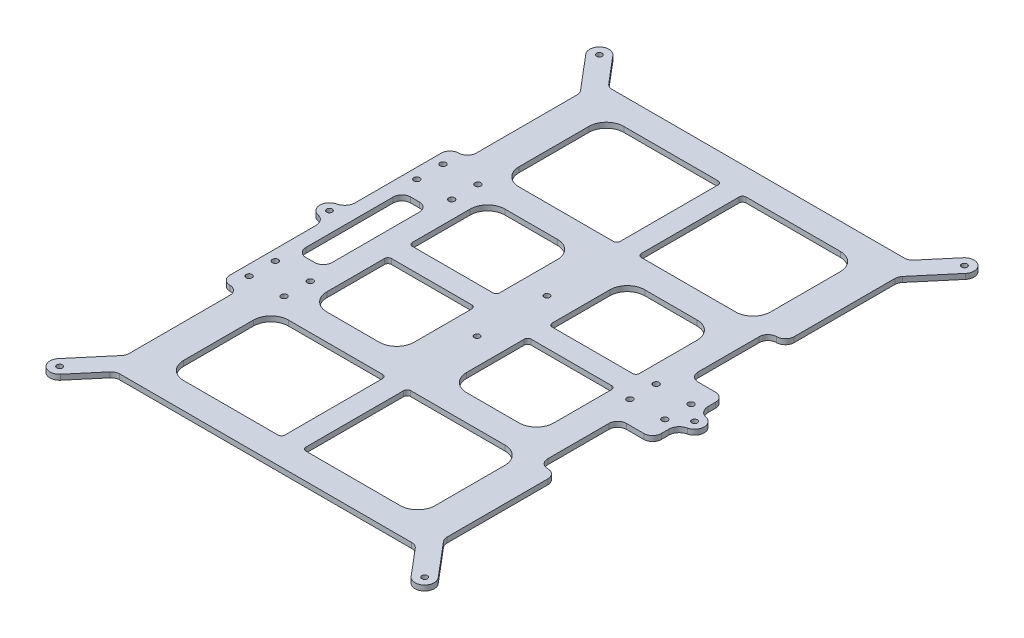
SolidWorks part; units mm, degrees
ref_plane "Alzado" through (0, 0, 0) normal (0, 0, 1) x (1, 0, 0)
ref_plane "Planta" through (0, 0, 0) normal (0, 1, 0) x (1, 0, 0)
ref_plane "Vista lateral" through (0, 0, 0) normal (1, 0, 0) x (0, 0, -1)
sketch "Croquis1" plane through (0, 0, 0) normal (0, 1, 0) x (1, 0, 0)
  line L0 (110, 320) -> (110, 0) construction
  line L1 (0, 0) -> (220, 0)
  line L2 (0, 0) -> (0, 320)
  line L3 (0, 320) -> (220, 320)
  line L4 (220, 0) -> (220, 320)
  line L5 (0, 160) -> (220, 160) construction
  line L6 (19, 320) -> (19, 0) construction
  line L7 (31, 320) -> (31, 0) construction
  line L8 (189, 320) -> (189, 0) construction
  line L9 (201, 320) -> (201, 0) construction
  line L10 (195, 320) -> (195, 0) construction
  line L11 (25, 320) -> (25, 0) construction
  line L12 (5.5, 314.5) -> (5.5, 160) construction
  circle A0 centre (185, 167.5) radius 1.7
  circle A1 centre (205, 167.5) radius 1.7
  circle A4 centre (185, 152.5) radius 1.7
  circle A5 centre (205, 152.5) radius 1.7
  circle A7 centre (35, 215.5) radius 1.7
  circle A8 centre (35, 200.5) radius 1.7
  circle A10 centre (35, 119.5) radius 1.7
  circle A13 centre (35, 104.5) radius 1.7
  circle A14 centre (5.5, 314.5) radius 1.6
  circle A15 centre (214.5, 314.5) radius 1.6
  circle A16 centre (214.5, 5.5) radius 1.6
  circle A17 centre (5.5, 5.5) radius 1.6
  circle A18 centre (15, 200.5) radius 1.7
  circle A19 centre (15, 215.5) radius 1.7
  circle A20 centre (15, 104.5) radius 1.7
  circle A21 centre (15, 119.5) radius 1.7
  circle A22 centre (110, 180) radius 1.6
  circle A23 centre (110, 140) radius 1.6
  circle A32 centre (5.5, 160) radius 1.6
  circle A37 centre (214.5, 160) radius 1.6
  dimension "D8" = 3.4
  dimension "D13" = 6
  dimension "D14" = 3.4
  dimension "D17" = 3.2
  dimension "D23" = 3.2
  dimension "D18" = 20
  dimension "D1" = 320
  dimension "D2" = 220
  dimension "D3" = 12
  dimension "D4" = 12
  dimension "D5" = 158
  dimension "D6" = 19
  dimension "D7" = 6
  dimension "D9" = 20
  dimension "D10" = 10
  dimension "D11" = 7.5
  dimension "D12" = 7.5
  dimension "D15" = 10
  dimension "D16" = 15
  dimension "D20" = 10
  dimension "D21" = 104.5
  dimension "D24" = 5.5
  dimension "D25" = 5.5
extrude "Saliente-Extruir1" add sketch "Croquis1" along normal blind 3
sketch "Croquis2" plane through (0, 3, 0) normal (0, 1, 0) x (1, 0, 0)
  line L0 (220, 160) -> (0, 160) construction
  line L2 (9, 9) -> (211, 9) construction
  line L3 (220, 0) -> (220, 320) construction
  line L4 (9, 148.775) -> (9, 94.5)
  line L5 (110, 320) -> (110, 0) construction
  line L6 (220, 320) -> (0, 320) construction
  line L7 (0, 0) -> (220, 0) construction
  line L8 (9, 9) -> (211, 9)
  line L9 (211, 9) -> (211, 311)
  line L10 (211, 311) -> (9, 311)
  line L11 (9, 311) -> (9, 9)
  line L15 (9, 225.5) -> (9, 171.225)
  line L16 (9, 225.5) -> (19, 225.5)
  line L18 (19, 94.5) -> (9, 94.5)
  line L19 (19, 94.5) -> (19, 30)
  line L20 (24.1066, 19) -> (195.8934, 19)
  line L21 (210.2988, 1.9504) -> (195.8934, 19)
  line L22 (1.2988, 9.0496) -> (19, 30)
  line L23 (9.7012, 1.9504) -> (24.1066, 19)
  line L24 (9, 148.775) -> (9, 9) construction
  line L25 (19, 148.775) -> (19, 19) construction
  line L26 (19, 19) -> (201, 19) construction
  line L27 (211, 9) -> (211, 311) construction
  line L28 (19, 225.5) -> (19, 290)
  line L29 (24.1066, 301) -> (195.8934, 301)
  line L30 (1.2988, 310.9504) -> (19, 290)
  line L31 (9.7012, 318.0496) -> (24.1066, 301)
  line L32 (0, 320) -> (0, 0) construction
  line L33 (218.7012, 9.0496) -> (201, 30)
  line L34 (201, 19) -> (201, 311) construction
  line L35 (201, 94.5) -> (201, 30)
  line L36 (201, 94.5) -> (211, 94.5)
  line L37 (211, 148.775) -> (211, 94.5)
  line L38 (211, 225.5) -> (211, 171.225)
  line L39 (211, 225.5) -> (201, 225.5)
  line L40 (201, 225.5) -> (201, 290)
  line L41 (218.7012, 310.9504) -> (201, 290)
  line L42 (210.2988, 318.0496) -> (195.8934, 301)
  line L43 (182, 276) -> (182, 236)
  line L44 (102, 286) -> (48, 286)
  line L46 (102, 226) -> (48, 226)
  line L47 (38, 276) -> (38, 236)
  line L48 (118, 226) -> (172, 226)
  line L52 (104, 284) -> (104, 228)
  line L53 (116, 284) -> (116, 228)
  line L54 (118, 286) -> (172, 286)
  line L55 (102, 94) -> (48, 94)
  line L56 (38, 44) -> (38, 84)
  line L57 (102, 34) -> (48, 34)
  line L58 (104, 36) -> (104, 92)
  line L59 (116, 36) -> (116, 92)
  line L60 (118, 34) -> (172, 34)
  line L61 (182, 44) -> (182, 84)
  line L62 (118, 94) -> (172, 94)
  line L63 (45, 152) -> (45, 119)
  line L64 (93, 166) -> (47, 166)
  line L65 (95, 168) -> (95, 201)
  line L66 (85, 211) -> (55, 211)
  line L67 (45, 168) -> (45, 201)
  line L68 (85, 109) -> (55, 109)
  line L69 (95, 152) -> (95, 119)
  line L70 (93, 154) -> (47, 154)
  line L71 (135, 109) -> (165, 109)
  line L72 (175, 152) -> (175, 119)
  line L73 (125, 152) -> (125, 119)
  line L74 (127, 154) -> (173, 154)
  line L75 (127, 166) -> (173, 166)
  line L76 (175, 168) -> (175, 201)
  line L77 (135, 211) -> (165, 211)
  line L78 (125, 168) -> (125, 201)
  arc A2 (1.2988, 9.0496) -> (9.7012, 1.9504) centre (5.5, 5.5) ccw
  arc A3 (4.3043, 165.3685) -> (4.3043, 154.6315) centre (5.5, 160) ccw
  arc A4 (9, 148.775) -> (4.3043, 154.6315) centre (3, 148.775) ccw
  arc A5 (9, 171.225) -> (4.3043, 165.3685) centre (3, 171.225) cw
  circle A6 centre (35, 215.5) radius 1.7 construction
  circle A7 centre (35, 104.5) radius 1.7 construction
  arc A8 (48, 226) -> (38, 236) centre (48, 236) cw
  arc A10 (1.2988, 310.9504) -> (9.7012, 318.0496) centre (5.5, 314.5) cw
  arc A11 (218.7012, 9.0496) -> (210.2988, 1.9504) centre (214.5, 5.5) cw
  arc A12 (211, 148.775) -> (215.6957, 154.6315) centre (217, 148.775) cw
  arc A13 (215.6957, 165.3685) -> (215.6957, 154.6315) centre (214.5, 160) cw
  arc A14 (211, 171.225) -> (215.6957, 165.3685) centre (217, 171.225) ccw
  arc A15 (218.7012, 310.9504) -> (210.2988, 318.0496) centre (214.5, 314.5) ccw
  arc A16 (48, 286) -> (38, 276) centre (48, 276) ccw
  arc A17 (172, 226) -> (182, 236) centre (172, 236) ccw
  arc A18 (172, 286) -> (182, 276) centre (172, 276) cw
  arc A19 (48, 94) -> (38, 84) centre (48, 84) ccw
  arc A20 (48, 34) -> (38, 44) centre (48, 44) cw
  arc A21 (172, 34) -> (182, 44) centre (172, 44) ccw
  arc A22 (172, 94) -> (182, 84) centre (172, 84) cw
  arc A23 (102, 226) -> (104, 228) centre (102, 228) ccw
  arc A24 (102, 286) -> (104, 284) centre (102, 284) cw
  arc A25 (116, 284) -> (118, 286) centre (118, 284) cw
  arc A26 (118, 226) -> (116, 228) centre (118, 228) cw
  arc A27 (116, 92) -> (118, 94) centre (118, 92) cw
  arc A28 (116, 36) -> (118, 34) centre (118, 36) ccw
  arc A29 (102, 34) -> (104, 36) centre (102, 36) ccw
  arc A30 (102, 94) -> (104, 92) centre (102, 92) cw
  arc A31 (95, 201) -> (85, 211) centre (85, 201) ccw
  arc A32 (55, 211) -> (45, 201) centre (55, 201) ccw
  arc A33 (55, 109) -> (45, 119) centre (55, 119) cw
  arc A34 (95, 119) -> (85, 109) centre (85, 119) cw
  arc A35 (165, 109) -> (175, 119) centre (165, 119) ccw
  arc A36 (125, 119) -> (135, 109) centre (135, 119) ccw
  arc A37 (165, 211) -> (175, 201) centre (165, 201) cw
  arc A38 (125, 201) -> (135, 211) centre (135, 201) cw
  arc A39 (127, 166) -> (125, 168) centre (127, 168) cw
  arc A40 (173, 166) -> (175, 168) centre (173, 168) ccw
  arc A41 (175, 152) -> (173, 154) centre (173, 152) ccw
  arc A42 (125, 152) -> (127, 154) centre (127, 152) cw
  arc A43 (45, 152) -> (47, 154) centre (47, 152) cw
  arc A44 (95, 152) -> (93, 154) centre (93, 152) ccw
  arc A45 (93, 166) -> (95, 168) centre (93, 168) ccw
  arc A46 (47, 166) -> (45, 168) centre (47, 168) cw
  point P28 (110, 19)
  point P71 (110, 301)
  point P76 (38, 226)
  point P79 (38, 286)
  point P106 (104, 226)
  point P109 (104, 286)
  point P112 (116, 286)
  point P115 (116, 226)
  point P118 (116, 94)
  point P121 (116, 34)
  point P124 (104, 34)
  point P127 (104, 94)
  point P137 (95, 211)
  point P140 (45, 211)
  point P167 (125, 166)
  point P170 (175, 166)
  point P173 (175, 154)
  point P176 (125, 154)
  point P179 (45, 154)
  point P182 (95, 154)
  point P185 (95, 166)
  point P188 (45, 166)
  dimension "D2" = 11
  dimension "D3" = 11
  dimension "D4" = 6
  dimension "D5" = 10
  dimension "D6" = 10
  dimension "D7" = 60
  dimension "D12" = 10
  dimension "D14" = 2
  dimension "D19" = 10
  dimension "D20" = 2
  dimension "D9" = 30
  dimension "D10" = 15
  dimension "D8" = 19
  dimension "D11" = 38
  dimension "D13" = 6
  dimension "D15" = 6
  dimension "D16" = 15
  dimension "D17" = 50
  dimension "D18" = 45
  dimension "D1" = 9
extrude "Cortar-Extruir1" cut sketch "Croquis2" against normal up to surface (3 mm away) flip side to cut up to face at (5.5, 0, -158.4)
fillet "Redondeo1" radius 5 12 edges at (9, 1.5, -225.5) (9, 1.5, -94.5) (24.1066, 1.5, -301) (195.8934, 1.5, -301) (201, 1.5, -290) (201, 1.5, -30) (195.8934, 1.5, -19) (24.1066, 1.5, -19) (19, 1.5, -30) (19, 1.5, -94.5) (19, 1.5, -290) (19, 1.5, -225.5)
sketch "Croquis3" plane through (0, 3, 0) normal (0, 1, 0) x (1, 0, 0)
  line L1 (211, 225.5) -> (191, 225.5)
  line L2 (211, 225.5) -> (211, 180.5)
  line L3 (211, 180.5) -> (191, 180.5)
  line L4 (191, 225.5) -> (191, 180.5)
  line L5 (211, 94.5) -> (191, 94.5)
  line L6 (211, 94.5) -> (211, 139.5)
  line L7 (211, 139.5) -> (191, 139.5)
  line L8 (191, 94.5) -> (191, 139.5)
  dimension "D1" = 45
  dimension "D2" = 45
  dimension "D3" = 20
  dimension "D4" = 20
extrude "Cortar-Extruir2" cut sketch "Croquis3" against normal up to surface (3 mm away) up to face at (70, 0, -186.9142)
sketch "Croquis4" plane through (0, 3, 0) normal (0, 1, 0) x (1, 0, 0)
  line L0 (9, 220.5) -> (9, 171.225) construction
  line L1 (17, 190) -> (32, 190)
  line L2 (17, 190) -> (17, 130)
  line L3 (17, 130) -> (32, 130)
  line L4 (32, 190) -> (32, 130)
  circle A0 centre (5.5, 160) radius 1.6 construction
  dimension "D3" = 30
  dimension "D1" = 15
  dimension "D2" = 60
  dimension "D4" = 8
extrude "Cortar-Extruir3" cut sketch "Croquis4" against normal up to surface (3 mm away) up to face at (112.8696, 0, -160)
fillet "Redondeo2" radius 5 12 edges at (201, 1.5, -94.5) (191, 1.5, -94.5) (191, 1.5, -139.5) (211, 1.5, -139.5) (211, 1.5, -180.5) (191, 1.5, -180.5) (191, 1.5, -225.5) (201, 1.5, -225.5) (32, 1.5, -190) (17, 1.5, -190) (17, 1.5, -130) (32, 1.5, -130)
